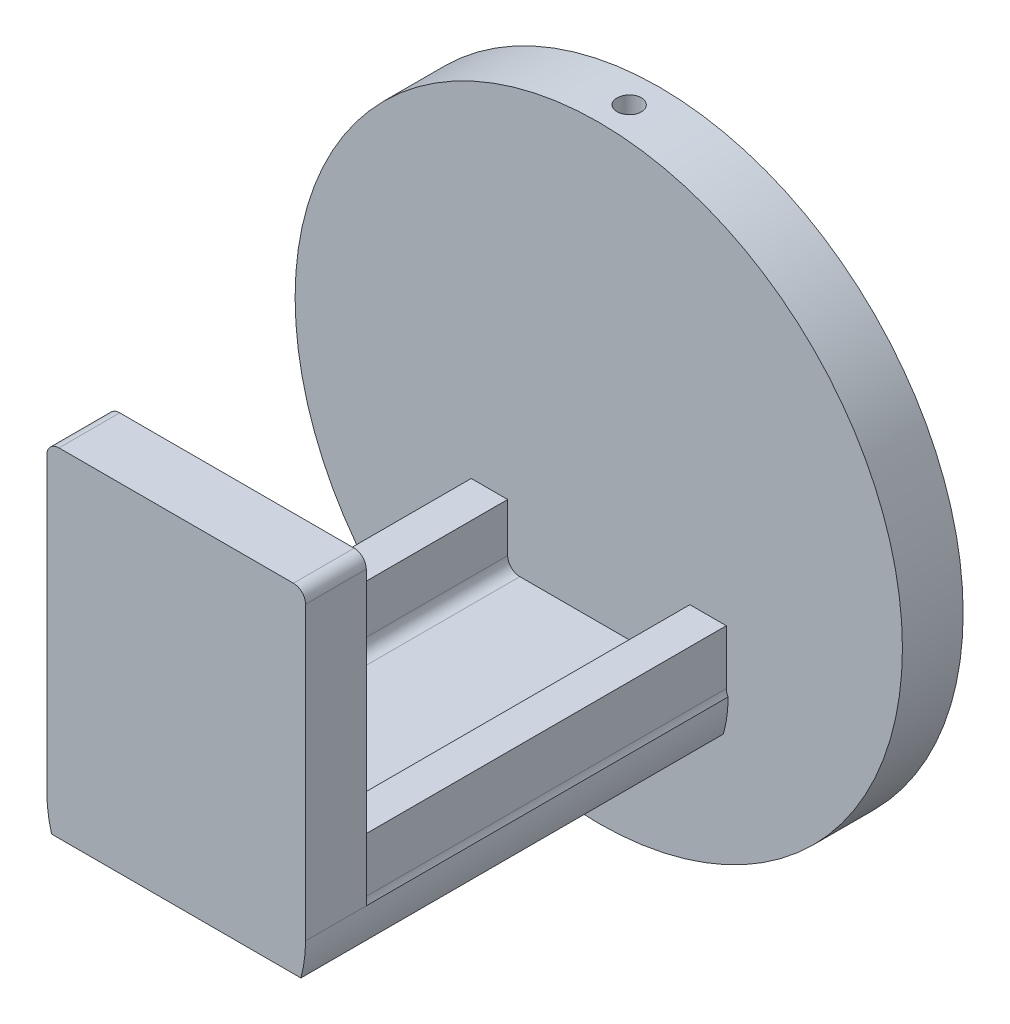
SolidWorks part; units mm, degrees
material "ABS"
ref_plane "Front Plane" through (0, 0, 0) normal (0, 0, 1) x (1, 0, 0)
ref_plane "Top Plane" through (0, 0, 0) normal (0, 1, 0) x (1, 0, 0)
ref_plane "Right Plane" through (0, 0, 0) normal (1, 0, 0) x (0, 0, -1)
sketch "Sketch1" plane through (0, 0, 0) normal (0, 0, 1) x (1, 0, 0)
  line L0 (-13.6056, -8.3607) -> (13.6056, -8.3607)
  line L1 (0, 25) -> (0, -11.3603) construction
  line L2 (-13.2709, -11.3603) -> (13.2709, -11.3603)
  circle A0 centre (0, 0) radius 25
  arc A1 (13.2709, -11.3603) -> (13.6056, -8.3607) centre (0, -8.3607) ccw
  arc A2 (-13.2709, -11.3603) -> (-13.6056, -8.3607) centre (0, -8.3607) cw
  point P5 (0, -8.3607)
  point P9 (0, -11.3603)
  dimension "D1" = 50
  dimension "D2" = 27.2113
  dimension "D3" = 26.5417
extrude "Boss-Extrude1" add sketch "Sketch1" against normal blind 5 contours A0
sketch "Sketch2" plane through (0, 0, 0) normal (0, 0, 1) x (1, 0, 0)
  line L0 (-10.65, -10.65) -> (10.65, -10.65)
  line L1 (0, 0) -> (0, -26.4743) construction
  line L2 (-10.2644, -13.49) -> (10.2644, -13.49)
  arc A0 (10.2644, -13.49) -> (10.65, -10.65) centre (0, -10.65) ccw
  arc A1 (-10.2644, -13.49) -> (-10.65, -10.65) centre (0, -10.65) cw
  point P5 (0, -10.65)
  point P8 (0, -13.49)
  dimension "D2" = 20.5287
  dimension "D3" = 10.65
  dimension "D1" = 21.3
  dimension "D4" = 10.65
extrude "Boss-Extrude2" add sketch "Sketch2" along normal blind 34.79
sketch "Sketch3" plane through (0, -10.65, 0) normal (0, 1, 0) x (1, 0, 0)
  line L0 (10.65, -29.79) -> (-10.65, -29.79)
  line L1 (10.65, -34.79) -> (10.65, 0) construction
  line L2 (-10.65, -34.79) -> (-10.65, 0) construction
  line L3 (-10.65, -29.79) -> (-10.65, -34.79)
  line L4 (-10.65, -34.79) -> (10.65, -34.79)
  line L5 (10.65, -34.79) -> (-10.65, -34.79) construction
  line L6 (10.65, -34.79) -> (10.65, -29.79)
  dimension "D1" = 5
extrude "Boss-Extrude3" add sketch "Sketch3" along normal blind 25
sketch "Sketch4" plane through (0, -10.65, 0) normal (0, 1, 0) x (1, 0, 0)
  line L0 (0, 0) -> (0, -34.79) construction
  line L1 (-10.65, -34.79) -> (10.65, -34.79) construction
  line L2 (7.5, 0) -> (7.5, -29.79)
  line L3 (10.65, 0) -> (-10.65, 0) construction
  line L4 (10.65, -29.79) -> (-10.65, -29.79) construction
  line L5 (7.5, -29.79) -> (10.5, -29.79)
  line L6 (10.5, -29.79) -> (10.5, 0)
  line L7 (10.5, 0) -> (7.5, 0)
  line L8 (-7.5, -29.79) -> (-10.5, -29.79)
  line L9 (-10.5, -29.79) -> (-10.5, 0)
  line L10 (-7.5, 0) -> (-7.5, -29.79)
  line L11 (-10.5, 0) -> (-7.5, 0)
  dimension "D1" = 7.5
  dimension "D2" = 3
extrude "Boss-Extrude5" add sketch "Sketch4" along normal blind 5
sketch "Sketch5" plane through (0, 0, 0) normal (0, 1, 0) x (1, 0, 0)
  line L0 (7.5, 0) -> (-7.5, 0) construction
  circle A0 centre (0, 2.5) radius 1
  dimension "D2" = 2
  dimension "D1" = 2.5
extrude "Cut-Extrude1" cut sketch "Sketch5" against normal through all and the other way blind 38 contours A0
fillet "Fillet1" radius 1 2 edges at (10.65, 14.35, 32.29) (-10.65, 14.35, 32.29)
fillet "Fillet2" radius 1 2 edges at (-7.5, -10.65, 14.895) (7.5, -10.65, 14.895)
fillet "Fillet3" radius 1 2 edges at (10.5, -10.65, 14.895) (-10.5, -10.65, 14.895)
sketch "Sketch6" plane through (0, 0, -5) normal (0, 0, -1) x (-1, 0, 0)
  line L0 (0, 25) -> (0, -25) construction
  line L1 (-25, 0) -> (25, 0) construction
  circle A0 centre (0, 0) radius 25 construction
  circle A1 centre (0, 11) radius 0.5
  circle A2 centre (0, -11) radius 0.5
  dimension "D1" = 1
  dimension "D2" = 11
extrude "Cut-Extrude2" cut sketch "Sketch6" against normal up to next
